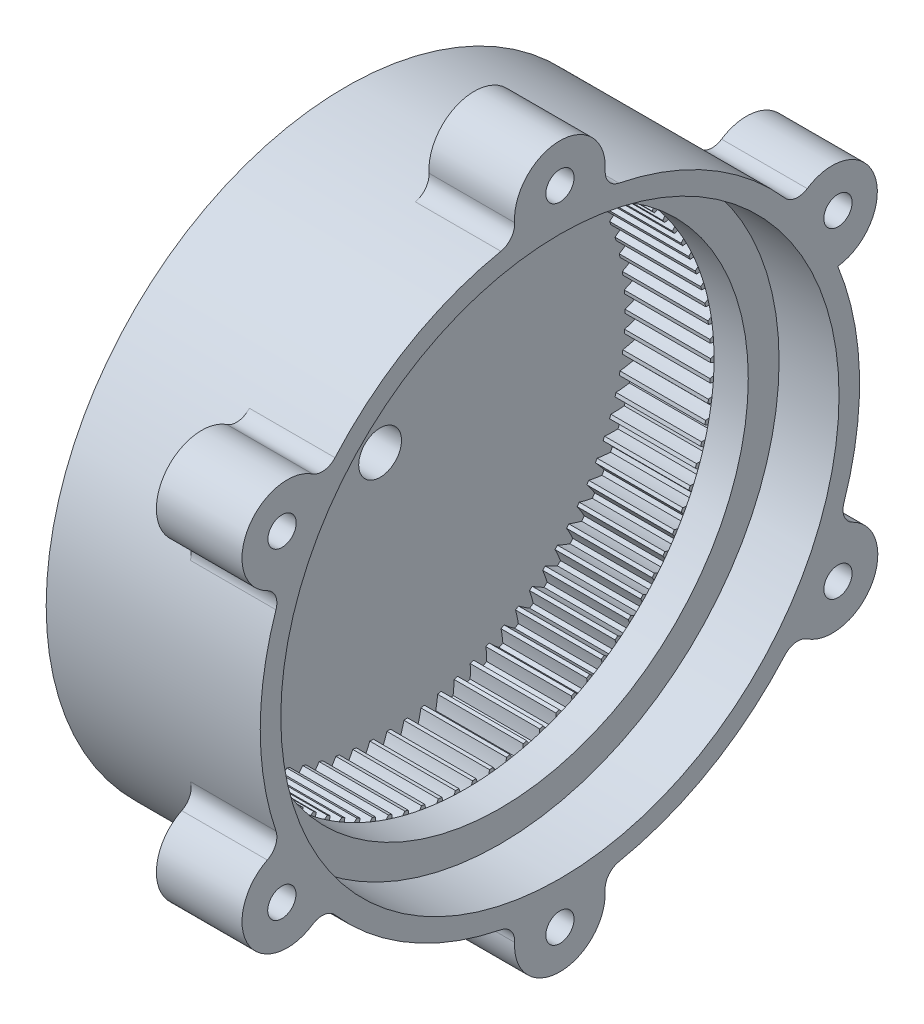
SolidWorks part; units mm, degrees
ref_plane "Plane1" through (0, 0, 0) normal (0, 0, 1) x (1, 0, 0)
ref_plane "Plane2" through (0, 0, 0) normal (0, 1, 0) x (1, 0, 0)
ref_plane "Plane3" through (0, 0, 0) normal (1, 0, 0) x (0, 0, -1)
sketch "HoldingSke" plane through (0, 0, 0) normal (0, 1, 0) x (1, 0, 0)
  line L0 (0, 0) -> (0, -1.5385)
  line L1 (-15, 0) -> (100, 0) construction
  line L2 (0, 0) -> (-2.1039, 2.3779)
  line L3 (0, 0) -> (-11.863, 4.5341)
  line L4 (0, 0) -> (0, 8.636)
  line L5 (0, 0) -> (-23.7986, -8.8762)
  line L6 (0, 0) -> (-10.5278, -7.1032)
  line L7 (-2.1039, 2.3779) -> (3.3635, 27.1825)
  line L8 (-76.2, 3.0279) -> (-54.61, 3.0279)
  line L9 (-71.009, 38.7566) -> (-53.1078, 45.2721)
  line L10 (-76.2, 71.12) -> (104.1128, 71.12)
  line L11 (0, 0) -> (-10, 0)
  line L12 (-76.2, 101.6) -> (-76.175, 101.6)
  line L13 (24.9733, 27.94) -> (52.9518, 28.4284)
  line L14 (24.9733, 27.94) -> (24.9743, 27.94)
  line L15 (24.9733, 27.94) -> (100.4006, 29.5858)
  circle A0 centre (0, 0) radius 35
  circle A1 centre (0, 0) radius 12.7
  circle A2 centre (0, 0) radius 12.7
  dimension "MHD" = 25.4
  dimension "Hub_dia" = 25.4
  dimension "Diameter" = 70
  dimension "Num_teeth" = 90
  dimension "Pitch" = 1.5385
  dimension "Overall_len" = 25.4
  dimension "Show_teeth" = 90
  dimension "Thickness" = 12.7
  dimension "OAL" = 25.4001
  dimension "T_dim" = 21.59
  dimension "Ap" = 20
  dimension "H" = 19.05
  dimension "Pitch_radius" = 180.3128
  dimension "Width" = 10
  dimension "Backlash" = 0.025
  dimension "Addendum_fac" = 1
  dimension "Dedendum_fac" = 1.25
  dimension "Clearance_fac" = 0.25
  dimension "Dedendum_add" = 0.001
  dimension "Module" = 0.65
sketch "BasProSke" plane through (0, 0, 0) normal (0, 1, 0) x (1, 0, 0)
  line L0 (-10, 0) -> (60, 0) construction
  line L1 (0, 28.6) -> (0, 35)
  line L2 (0, 28.6) -> (10, 28.6)
  line L3 (10, 28.6) -> (10, 35)
  line L4 (10, 35) -> (0, 35)
  dimension "Diameter" = 70
  dimension "Thickness" = 10
  dimension "Inside_diameter" = 57.2
revolve "Base-Revolve" add sketch "BasProSke" angle 360 about L0
sketch "TooCutSke" plane through (0, 0, 0) normal (1, 0, 0) x (0, 0, -1)
  line L3 (0.573, 29.2444) -> (0.573, 53.6633) construction
  line L4 (0, 0) -> (0, 59.563) construction
  line L5 (0, 0) -> (-2.3846, 68.2859) construction
  line L6 (-13.188, 24.292) -> (36.9564, 26.043) construction
  circle A0 centre (0, 0) radius 29.25 construction
  circle A1 centre (0, 0) radius 30.0635 construction
  circle A2 centre (0, 0) radius 24.7374 construction
  circle A3 centre (0, 0) radius 28.5746 construction
  arc A4 (0.7993, 28.5634) -> (0.2505, 30.0625) centre (-13.188, 24.292) ccw
  arc A5 (0.7993, 28.5634) -> (-0.7993, 28.5634) centre (0, 0) ccw
  arc A6 (0.2505, 30.0625) -> (-0.2505, 30.0625) centre (0, 0) ccw
  arc A7 (-0.2505, 30.0625) -> (-0.7993, 28.5634) centre (13.188, 24.292) ccw
  dimension "Pitch_dia" = 58.5
  dimension "Base_dia" = 49.4748
  dimension "Root_dia" = 60.127
  dimension "Overcut_dia" = 57.1492
  dimension "Flank_rad" = 14.625
  dimension "Half_ang" = 2
  dimension "Half_CT" = 0.573
extrude "ToothCut" cut sketch "TooCutSke" along normal through all
fillet "Breaks" [suppressed] radius 0.065
fillet "RootFillets" [suppressed] radius 0.1635
pattern_circular "TeethCuts" count 90 every 4 about axis through (-10, 0, 0) along (1, 0, 0) of "RootFillets", "Breaks", "ToothCut"
sketch "Sketch1" plane through (0, 0, 0) normal (-1, 0, 0) x (0, 0, 1)
  circle A0 centre (0, 0) radius 35
  dimension "D1" = 70
extrude "Boss-Extrude1" add sketch "Sketch1" along normal blind 4
sketch "Sketch2" plane through (-4, 0, 0) normal (-1, 0, 0) x (0, 0, 1)
  circle A0 centre (0, 0) radius 2.5
  dimension "D1" = 5
extrude "Cut-Extrude1" cut sketch "Sketch2" against normal blind 4
sketch "Sketch3" plane through (10, 0, 0) normal (1, 0, 0) x (0, 0, -1)
  circle A0 centre (0, 0) radius 29
  circle A1 centre (0, 0) radius 35
  dimension "D1" = 58
extrude "Boss-Extrude2" add sketch "Sketch3" along normal blind 4
sketch "Sketch4" plane through (14, 0, 0) normal (1, 0, 0) x (0, 0, -1)
  circle A0 centre (0, 0) radius 32.6
  circle A1 centre (0, 0) radius 35
  dimension "D1" = 65.2
extrude "Boss-Extrude3" add sketch "Sketch4" along normal blind 7
sketch "Sketch5" plane through (21, 0, 0) normal (1, 0, 0) x (0, 0, -1)
  line L0 (0, 0) -> (0, -42) construction
  line L1 (0, 0) -> (-36.3731, 21) construction
  line L2 (0, 0) -> (36.3731, 21) construction
  line L3 (0, 0) -> (-4.8711, -34.6594) construction
  line L4 (0, 0) -> (4.8711, -34.6594) construction
  line L5 (0, 0) -> (27.5804, 21.5482) construction
  line L6 (0, 0) -> (32.4514, 13.1112) construction
  line L7 (0, 0) -> (-32.4514, 13.1112) construction
  line L8 (0, 0) -> (-27.5804, 21.5482) construction
  arc A0 (27.5804, 21.5482) -> (32.4514, 13.1112) centre (0, 0) cw
  circle A12 centre (0, 0) radius 35 construction
  arc A13 (4.8711, -34.6594) -> (-4.8711, -34.6594) centre (0, 0) cw
  arc A14 (4.8711, -34.6594) -> (-4.8711, -34.6594) centre (0, 0) cw
  arc A15 (4.8711, -34.6594) -> (-4.8711, -34.6594) centre (0, -36.7275) cw
  arc A16 (32.4514, 13.1112) -> (27.5804, 21.5482) centre (31.7896, 18.3538) ccw
  arc A17 (-32.4514, 13.1112) -> (-27.5804, 21.5482) centre (0, 0) cw
  arc A18 (-32.4514, 13.1112) -> (-27.5804, 21.5482) centre (-31.8295, 18.3768) cw
  circle M5 centre (0, 0) radius 35
  dimension "D1" = 8
  dimension "D2" = 8
  dimension "D3" = 8
  dimension "D4" = 8
  dimension "D5" = 8
  dimension "D6" = 8
extrude "Boss-Extrude4" add sketch "Sketch5" against normal blind 10 contours M5 | A16 A0 | A18 A17 region at (21, -38.0165, 0)
fillet "Fillet3" radius 2 5 edges at (16, -34.6594, -4.8711) (16, -34.6594, 4.8711) (16, 13.1112, 32.4514) (16, 21.5482, 27.5804) (16, 21.5482, -27.5804)
sketch "Sketch8" plane through (21, 0, 0) normal (1, 0, 0) x (0, 0, -1)
  line L0 (0, 0) -> (32.476, 18.75) construction
  line L1 (0, 0) -> (0, -37.5) construction
  line L2 (0, 0) -> (-32.4511, 18.793) construction
  circle A0 centre (32.476, 18.75) radius 1.65
  circle A1 centre (0, -37.5) radius 1.65
  circle A2 centre (-32.4511, 18.793) radius 1.65
  dimension "D2" = 3.3
  dimension "D1" = 37.5
extrude "Cut-Extrude2" cut sketch "Sketch8" against normal blind 10
sketch "Sketch9" plane through (21, 0, 0) normal (1, 0, 0) x (0, 0, -1)
  line L0 (0, 0) -> (32.476, 18.75) construction
  line L1 (0, 0) -> (36.3731, -21) construction
  line L2 (0, 0) -> (-36.3731, -21) construction
  line L3 (0, 0) -> (0, 42) construction
  line L4 (0, 0) -> (27.5804, -21.5482) construction
  line L5 (0, 0) -> (32.4514, -13.1112) construction
  line L6 (0, 0) -> (27.5804, -21.5482) construction
  arc A0 (6.8846, -34.3162) -> (32.4514, 13.1112) centre (0, 0) ccw construction
  arc A1 (27.5804, -21.5482) -> (32.4514, -13.1112) centre (0, 0) ccw
  arc A2 (32.4514, -13.1112) -> (27.5804, -21.5482) centre (31.8284, -18.3761) cw
  arc A3 (-27.5804, -21.5482) -> (-32.4514, -13.1112) centre (-31.8284, -18.3761) cw
  arc A4 (-4.8711, 34.6594) -> (4.8711, 34.6594) centre (0, 36.7523) cw
  arc M14 (6.8846, -34.3162) -> (32.4514, 13.1112) centre (0, 0) ccw
  arc M17 (26.2806, 23.1156) -> (-26.271, 23.1265) centre (0, 0) ccw
  arc M21 (-33.1636, 11.1881) -> (-6.8846, -34.3162) centre (0, 0) ccw
  dimension "D1" = 60
  dimension "D2" = 120
  dimension "D3" = 60
  dimension "D4" = 8
  dimension "D5" = 8
  dimension "D7" = 35
  dimension "D6" = 3
extrude "Boss-Extrude5" add sketch "Sketch9" against normal blind 10 contours A2 M14 | A4 M17 | A3 M21 region at (21, -19.0166, -32.9377) region at (21, -19.0166, 32.9377) region at (21, 38.0332, 0)
sketch "Sketch10" plane through (21, 0, 0) normal (1, 0, 0) x (0, 0, -1)
  line L0 (0, 0) -> (32.476, -18.75) construction
  line L1 (0, 0) -> (32.476, -18.75) construction
  circle A0 centre (32.476, -18.75) radius 1.65
  circle A1 centre (-32.476, -18.75) radius 1.65
  circle A2 centre (0, 37.5) radius 1.65
  dimension "D1" = 3.3
  dimension "D3" = 37.5
  dimension "D2" = 3
extrude "Cut-Extrude3" cut sketch "Sketch10" against normal blind 10
fillet "Fillet4" radius 2 6 edges at (16, -13.1112, -32.4514) (16, -21.5482, -27.5804) (16, -21.5482, 27.5804) (16, -13.1112, 32.4514) (16, 34.6594, 4.8711) (16, 34.6594, -4.8711)
equation "' \"Module@HoldingSke\" = 6.35"
equation "' \"Num_teeth@HoldingSke\" = 24"
equation "' \"Ap@HoldingSke\" =  14.5"
equation "' \"Ap@HoldingSke\" = 14.5"
equation "' \"Width@HoldingSke\" = 12"
equation "' \"Diameter@HoldingSke\" = 8 * 25.4"
equation "' \"Show_teeth@HoldingSke\" = 100"
equation "' \"Backlash@HoldingSke\" = 0.009 * 25.4"
equation "' \"Addendum_fac@HoldingSke\" = 1.0"
equation "' \"Dedendum_fac@HoldingSke\" = 1.25"
equation "' \"Dedendum_add@HoldingSke\" = 0.00005 * 25.4"
equation "' \"Clearance_fac@HoldingSke\" = 0.25"
equation "\"Pitch@HoldingSke\" = 1 / \"Module@HoldingSke\" "
equation "\"Overcut_dia@TooCutSke\" = (\"Num_teeth@HoldingSke\" - 2 * \"Addendum_fac@HoldingSke\") / \"Pitch@HoldingSke\" - 0.002 * 25.4"
equation "\"Pitch_dia@TooCutSke\" = \"Num_teeth@HoldingSke\" / \"Pitch@HoldingSke\""
equation "\"Base_dia@TooCutSke\" = \"Num_teeth@HoldingSke\" / \"Pitch@HoldingSke\" * cos((\"Ap@HoldingSke\"  * 3.14159265 / 180)) * 0.90"
equation "\"Root_dia@TooCutSke\" = \"Num_teeth@HoldingSke\"  / \"Pitch@HoldingSke\" + 2 *  \"Dedendum_fac@HoldingSke\"/ \"Pitch@HoldingSke\" + \"Dedendum_add@HoldingSke\" * 2"
equation "\"Half_ang@TooCutSke\" = 180 / \"Num_teeth@HoldingSke\""
equation "\"Half_CT@TooCutSke\" = \"Num_teeth@HoldingSke\" / \"Pitch@HoldingSke\" * sin((3.14159265 / 2 / \"Num_teeth@HoldingSke\")) / 2 + 10 * \"Backlash@HoldingSke\" / 4"
equation "\"Flank_rad@TooCutSke\" = \"Num_teeth@HoldingSke\" / \"Pitch@HoldingSke\" / 4"
equation "\"Radius@RootFillets\"= \"Clearance_fac@HoldingSke\" / \"Pitch@HoldingSke\" + \"Dedendum_add@HoldingSke\""
equation "\"Break_rad@Breaks\" = 0.02 / \"Pitch@HoldingSke\" * 5"
equation "\"Num_teeth@TeethCuts\" = int( \"Show_teeth@HoldingSke\" ) + 1"
equation "\"Num_teeth@TeethCuts\" = ((sgn( \"Num_teeth@TeethCuts\" - \"Num_teeth@HoldingSke\" )-1)*( \"Num_teeth@TeethCuts\" - \"Num_teeth@HoldingSke\" ))/-2+ \"Num_teeth@HoldingSke\""
equation "\"Num_teeth@TeethCuts\" = ((sgn( \"Num_teeth@TeethCuts\" - 2.0)+1)*( \"Num_teeth@TeethCuts\" - 2.0))/2 +2.0"
equation "\"Angle@TeethCuts\" = 360.0 / \"Num_teeth@HoldingSke\""
equation "\"Diameter@BasProSke\" = \"Num_teeth@HoldingSke\"  / \"Pitch@HoldingSke\" + 2 *  \"Dedendum_fac@HoldingSke\"/ \"Pitch@HoldingSke\" + \"Dedendum_add@HoldingSke\" * 2 + 0.002 * 25.4"
equation "\"Diameter@BasProSke\" = ((sgn( \"Diameter@BasProSke\"  - \"Diameter@HoldingSke\" )+1)*( \"Diameter@BasProSke\"  - \"Diameter@HoldingSke\" ))/2 + \"Diameter@HoldingSke\""
equation "\"Inside_diameter@BasProSke\" =  (\"Num_teeth@HoldingSke\" - 2 * \"Addendum_fac@HoldingSke\") / \"Pitch@HoldingSke\" "
equation "\"Thickness@BasProSke\"  = \"Width@HoldingSke\""
